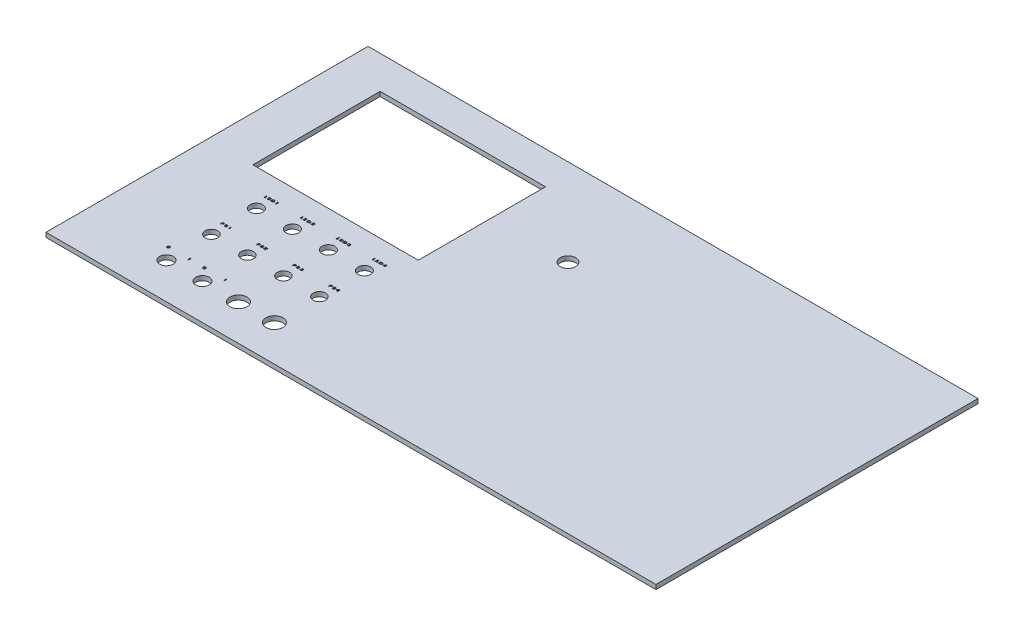
SolidWorks part; units mm, degrees
ref_plane "Front Plane" through (0, 0, 0) normal (0, 0, 1) x (1, 0, 0)
ref_plane "Top Plane" through (0, 0, 0) normal (0, 1, 0) x (1, 0, 0)
ref_plane "Right Plane" through (0, 0, 0) normal (1, 0, 0) x (0, 0, -1)
sketch "Sketch1" plane through (0, 0, 0) normal (0, 1, 0) x (1, 0, 0)
  line L1 (0, 0) -> (861.06, 0)
  line L2 (0, 0) -> (0, 454.66)
  line L3 (0, 454.66) -> (861.06, 454.66)
  line L4 (861.06, 0) -> (861.06, 454.66)
  dimension "D1" = 861.06
  dimension "D2" = 454.66
extrude "Boss-Extrude1" add sketch "Sketch1" along normal blind 6.35
sketch "Sketch3" plane through (0, 6.35, 0) normal (0, 1, 0) x (1, 0, 0)
  line L0 (0, 0) -> (861.06, 0) construction
  line L1 (63.5, 408.178) -> (296.926, 408.178)
  line L2 (63.5, 408.178) -> (63.5, 228.6)
  line L3 (63.5, 228.6) -> (296.926, 228.6)
  line L4 (296.926, 408.178) -> (296.926, 228.6)
  line L5 (0, 454.66) -> (0, 0) construction
  point P4 (180.213, 228.6)
  point P7 (63.5, 318.389)
  dimension "D1" = 233.426
  dimension "D2" = 179.578
  dimension "D3" = 228.6
  dimension "D4" = 63.5
extrude "Cut-Extrude2" cut sketch "Sketch3" against normal through all
sketch "Sketch4" plane through (0, 6.35, 0) normal (0, 1, 0) x (1, 0, 0)
  line L2 (63.5, 228.6) -> (296.926, 228.6) construction
  line L4 (170.053, 177.8) -> (220.853, 177.8) construction
  circle A0 centre (119.253, 177.8) radius 9.017
  circle A1 centre (170.053, 177.8) radius 9.017
  circle A2 centre (220.853, 177.8) radius 9.017
  circle A3 centre (271.653, 177.8) radius 9.017
  point P11 (195.453, 177.8)
  point P12 (180.213, 228.6)
  dimension "D1" = 18.034
  dimension "D3" = 50.8
  dimension "D4" = 15.24
  dimension "D5" = 50.8
  dimension "D2" = 4
extrude "Cut-Extrude3" cut sketch "Sketch4" against normal through all
sketch "Sketch5" plane through (0, 6.35, 0) normal (0, 1, 0) x (1, 0, 0)
  circle A0 centre (119.253, 114.3) radius 8.763
  circle A1 centre (170.053, 114.3) radius 8.763
  circle A2 centre (220.853, 114.3) radius 8.763
  circle A3 centre (271.653, 114.3) radius 8.763
  circle A4 centre (119.253, 177.8) radius 9.017 construction
  dimension "D1" = 17.526
  dimension "D3" = 63.5
  dimension "D2" = 4
extrude "Cut-Extrude4" cut sketch "Sketch5" against normal through all
sketch "Sketch6" plane through (0, 6.35, 0) normal (0, 1, 0) x (1, 0, 0)
  circle A0 centre (119.253, 50.8) radius 9.525
  circle A1 centre (170.053, 50.8) radius 9.525
  circle A4 centre (271.653, 50.8) radius 9.525 [skipped]
  circle A5 centre (220.853, 50.8) radius 9.525 [skipped]
  dimension "D1" = 19.05
  dimension "D3" = 63.5
  dimension "D2" = 4
extrude "Cut-Extrude5" cut sketch "Sketch6" against normal through all
sketch "Sketch7" plane through (0, 6.35, 0) normal (0, 1, 0) x (1, 0, 0)
  circle A0 centre (220.853, 50.8) radius 11.938
  circle A1 centre (271.653, 50.8) radius 11.938
  circle A4 centre (373.253, 50.8) radius 11.938 [skipped]
  circle A5 centre (322.453, 50.8) radius 11.938 [skipped]
  dimension "D3" = 23.876
  dimension "D1" = 4
extrude "Cut-Extrude6" cut sketch "Sketch7" against normal through all
sketch "Sketch8" plane through (0, 6.35, 0) normal (0, 1, 0) x (1, 0, 0)
  line L0 (0, 454.66) -> (0, 0) construction
  circle A0 centre (119.253, 177.8) radius 9.017 construction
  circle A1 centre (119.253, 114.3) radius 8.763 construction
  arc A2 (106.553, 66.6623) -> (131.953, 66.6623) centre (119.253, 50.8) cw construction
  arc A3 (157.353, 66.6623) -> (182.753, 66.6623) centre (170.053, 50.8) cw construction
  text T0 "LED1\r\n" font "Century Gothic" height 3.5
  text T1 "LED2" font "Century Gothic" height 3.5
  text T2 "PB1" font "Century Gothic" height 3.5
  text T3 "LED3" font "Century Gothic" height 3.5
  text T4 "LED4" font "Century Gothic" height 3.5
  text T5 "PB2" font "Century Gothic" height 3.5
  text T6 "PB3" font "Century Gothic" height 3.5
  text T7 "PB4" font "Century Gothic" height 3.5
  text T8 "0" font "Century Gothic" height 3.5
  text T9 "1" font "Century Gothic" height 3.5
  text T10 "0" font "Century Gothic" height 3.5
  text T11 "1" font "Century Gothic" height 3.5
  point P20 (119.253, 71.12)
  dimension "D11" = 20.32
  dimension "D1" = 110.49
  dimension "D2" = 19.05
  dimension "D3" = 50.8
  dimension "D4" = 101.6
  dimension "D5" = 152.4
  dimension "D6" = 112.268
  dimension "D7" = 19.05
  dimension "D8" = 50.8041
  dimension "D9" = 101.6
  dimension "D10" = 152.4
  dimension "D12" = 25.4
  dimension "D13" = 2
extrude "Cut-Extrude7" cut sketch "Sketch8" against normal blind 1.27
sketch "Sketch9" plane through (0, 6.35, 0) normal (0, 1, 0) x (1, 0, 0)
  line L0 (296.926, 228.6) -> (296.926, 408.178) construction
  line L1 (296.926, 408.178) -> (63.5, 408.178) construction
  circle A0 centre (404.876, 331.978) radius 10.922
  dimension "D1" = 21.844
  dimension "D2" = 107.95
  dimension "D3" = 76.2
extrude "Cut-Extrude8" cut sketch "Sketch9" against normal through all
